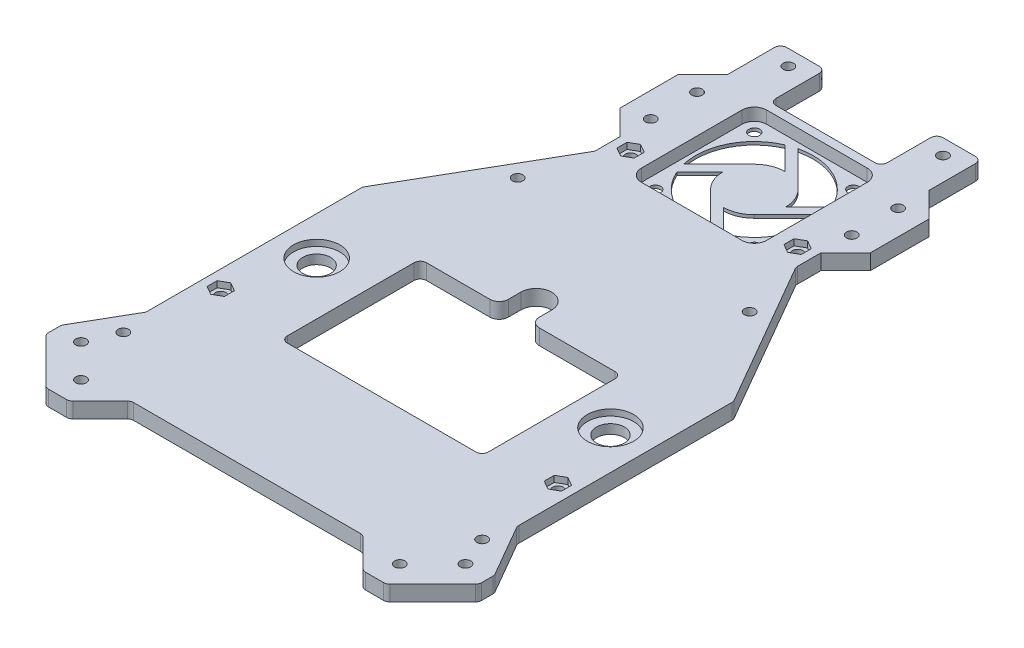
SolidWorks part; units mm, degrees
material "ABS PC"
ref_plane "Front Plane" through (0, 0, 0) normal (0, 0, 1) x (1, 0, 0)
ref_plane "Top Plane" through (0, 0, 0) normal (0, 1, 0) x (1, 0, 0)
ref_plane "Right Plane" through (0, 0, 0) normal (1, 0, 0) x (0, 0, -1)
sketch "Sketch1" plane through (0, 0, 0) normal (0, 1, 0) x (1, 0, 0)
  line L1 (70, -110) -> (-70, -110)
  line L2 (70, -110) -> (70, 110)
  line L3 (70, 110) -> (-70, 110)
  line L4 (-70, -110) -> (-70, 110)
  line L5 (70, -110) -> (-70, 110) construction
  line L6 (70, 110) -> (-70, -110) construction
  point P0 (0, 0)
  dimension "D1" = 220
  dimension "D2" = 140
extrude "Boss-Extrude1" add sketch "Sketch1" along normal blind 5
sketch "Sketch8" plane through (0, 5, 0) normal (0, 1, 0) x (1, 0, 0)
  line L0 (-70, 110) -> (-32.5, 110)
  line L1 (70, 110) -> (-70, 110) construction
  line L2 (-32.5, 110) -> (-32.5, 44.9519)
  line L3 (-32.5, 44.9519) -> (-70, -20)
  line L4 (-70, 110) -> (-70, -110) construction
  line L5 (-70, 110) -> (-70, -20)
  line L6 (0, 110) -> (0, -110) construction
  line L7 (-70, -110) -> (70, -110) construction
  line L8 (70, 110) -> (70, -20)
  line L9 (32.5, 44.9519) -> (70, -20)
  line L10 (32.5, 110) -> (32.5, 44.9519)
  line L11 (70, 110) -> (32.5, 110)
  dimension "D1" = 130
  dimension "D2" = 30
  dimension "D3" = 65
extrude "Cut-Extrude1" cut sketch "Sketch8" against normal blind 5
chamfer "Chamfer3" distance 15 angle 45 2 edges at (70, 2.5, 110) (-70, 2.5, 110)
sketch "Sketch48" plane through (0, 5, 0) normal (0, 1, 0) x (1, 0, 0)
  line L0 (32.5, 110) -> (-32.5, 110) construction
  line L1 (34.2449, 70.5) -> (40.5, 70.5) construction
  line L2 (32.5, 53) -> (32.5, 88)
  line L4 (32.5, 88) -> (40.5, 80)
  line L5 (40.5, 80) -> (40.5, 61)
  line L6 (32.5, 53) -> (40.5, 61)
  line L7 (0, 71.0199) -> (0, 60.9015) construction
  line L8 (-32.5, 53) -> (-40.5, 61)
  line L9 (-40.5, 80) -> (-40.5, 61)
  line L10 (-32.5, 88) -> (-40.5, 80)
  line L11 (-32.5, 53) -> (-32.5, 88)
  line L13 (32.5, 110) -> (32.5, 44.9519) construction
  point P0 (32.5, 83)
  point P16 (-32.5, 70.5)
  point P21 (0, 0)
  point P22 (36.7334, 83)
  dimension "D1" = 45
  dimension "D2" = 8
  dimension "D3" = 35
  dimension "D4" = 39.5
extrude "Boss-Extrude4" add sketch "Sketch48" against normal up to surface (5 mm away) up to face at (0, 0, 14.0096)
sketch "Sketch10" plane through (0, 0, 0) normal (0, 1, 0) x (1, 0, 0)
  line L0 (0, 110) -> (0, -110) construction
  line L1 (32.5, 110) -> (-32.5, 110) construction
  line L2 (-55, -110) -> (55, -110) construction
  line L3 (-32.5, 78) -> (-32.5, 63) construction
  line L4 (-62.5, -102.5) -> (-56.8431, -96.8431) construction
  line L5 (-62.1464, -91.5398) -> (-51.5398, -102.1464) construction
  line L6 (-70, -95) -> (-55, -110) construction
  point P9 (32.5, 63)
  point P10 (32.5, 78)
  point P17 (51.5398, -102.1464)
  point P18 (62.1464, -91.5398)
  dimension "D1" = 15
  dimension "D2" = 65
  dimension "D3" = 32
  dimension "D4" = 15
  dimension "D5" = 8
sketch "Sketch15" plane through (0, 5, 0) normal (0, 1, 0) x (1, 0, 0)
  line L0 (0, 110) -> (0, -110) construction
  line L1 (32.5, 110) -> (-32.5, 110) construction
  line L2 (-55, -110) -> (55, -110) construction
  line L3 (25, 100) -> (-25, 100) construction
  line L4 (37.5, 25) -> (-37.5, 25) construction
  line L5 (58, -57) -> (-58, -57) construction
  point P9 (0, 100)
  point P13 (0, 25)
  point P15 (0, -57)
  dimension "D1" = 50
  dimension "D2" = 10
  dimension "D3" = 75
  dimension "D4" = 85
  dimension "D5" = 116
  dimension "D6" = 167
hole_wizard "CSK for M3 Flat Head Machine Screw3" positions "Sketch16" profile "Sketch17" countersink size "M3" standard "ANSI Metric"
sketch "Sketch16" plane through (0, 0, 0) normal (0, 1, 0) x (1, 0, 0)
  point P6 (37.5, 25)
  point P9 (-37.5, 25)
  point P12 (-25, 100)
  point P15 (25, 100)
sketch "Sketch17" plane through (37.5, 0, -25) normal (1, 0, 0) x (0, 0, -1)
  line L0 (0, 0) -> (0, 6.0215)
  line L1 (0, 6.0215) -> (1.7, 5)
  line L2 (1.7, 5) -> (1.7, 1.45)
  line L3 (1.7, 1.45) -> (3.15, 0)
  line L5 (3.15, 0) -> (0, 0)
  line L6 (-1.7, 1.45) -> (-3.15, 0) construction
  line L10 (0, 6.0215) -> (-1.7, 5) construction
  line L11 (0, -6.35) -> (0, 107.95) construction
  dimension "Hole Dia." = 3.4
  dimension "Hole Depth" = 5
  dimension "Near C'Sink Dia." = 6.3
  dimension "Near C'Sink Angle" = 90
  dimension "Drill Angle" = 118
sketch "Sketch18" plane through (0, 5, 0) normal (0, 1, 0) x (1, 0, 0)
  line L0 (32.5, 110) -> (-32.5, 110) construction
  line L1 (-46.4338, 114.6286) -> (34.8035, 114.6286)
  line L2 (-46.4338, 114.6286) -> (-46.4338, 105)
  line L3 (-46.4338, 105) -> (34.8035, 105)
  line L4 (34.8035, 114.6286) -> (34.8035, 105)
  dimension "D1" = 5
extrude "Cut-Extrude2" cut sketch "Sketch18" against normal blind 5
sketch "Sketch34" plane through (0, 5, 0) normal (0, 1, 0) x (1, 0, 0)
  line L0 (-70, -20) -> (-60, -2.6795)
  line L1 (-70, -20) -> (-32.5, 44.9519) construction
  line L2 (-60, -2.6795) -> (-60, -72.6795)
  line L3 (-60, -72.6795) -> (-70, -90)
  line L4 (-70, -20) -> (-70, -95) construction
  line L5 (-70, -90) -> (-70, -20)
  line L6 (0, -90.4055) -> (0, -61.6307) construction
  line L7 (70, -90) -> (70, -20)
  line L8 (60, -72.6795) -> (70, -90)
  line L9 (60, -2.6795) -> (60, -72.6795)
  line L10 (70, -20) -> (60, -2.6795)
  line L11 (-55, -110) -> (55, -110) construction
  dimension "D1" = 120
  dimension "D2" = 20
extrude "Cut-Extrude8" cut sketch "Sketch34" against normal blind 10
chamfer "Chamfer4" [suppressed] distance 20 angle 30
sketch "Sketch35" plane through (0, 5, 0) normal (0, 1, 0) x (1, 0, 0)
  line L1 (-30.5, -58.5) -> (34.5, -58.5)
  line L2 (-30.5, -58.5) -> (-30.5, -13.5)
  line L3 (-30.5, -13.5) -> (34.5, -13.5)
  line L4 (34.5, -58.5) -> (34.5, -13.5)
  line L5 (-30.5, -58.5) -> (34.5, -13.5) construction
  line L6 (-30.5, -13.5) -> (34.5, -58.5) construction
  point P0 (2, -36)
  dimension "D1" = 2
  dimension "D2" = 65
  dimension "D3" = 45
  dimension "D4" = 36
extrude "Cut-Extrude9" cut sketch "Sketch35" against normal through all
fillet "Fillet1" radius 2 4 edges at (-30.5, 2.5, 58.5) (-30.5, 2.5, 13.5) (34.5, 2.5, 13.5) (34.5, 2.5, 58.5)
sketch "Sketch36" plane through (0, 5, 0) normal (0, 1, 0) x (1, 0, 0)
  line L0 (0, -110) -> (0, -100) construction
  line L1 (-55, -110) -> (55, -110) construction
  line L2 (-47.5, -110) -> (-37.5, -100)
  line L3 (-37.5, -100) -> (37.5, -100)
  line L4 (-47.5, -110) -> (47.5, -110)
  line L6 (-70, -95) -> (-55, -110) construction
  line L7 (47.5, -110) -> (37.5, -100)
  dimension "D1" = 10
  dimension "D2" = 95
extrude "Cut-Extrude10" cut sketch "Sketch36" against normal through all
sketch "Sketch38" plane through (0, 0, 0) normal (0, -1, 0) x (1, 0, 0)
  line L0 (0, -105) -> (0, -90) construction
  line L1 (-32.5, -105) -> (32.5, -105) construction
  line L2 (18, -87) -> (-18, -87)
  line L3 (-18, -87) -> (-18, -105)
  line L4 (-18, -105) -> (18, -105)
  line L5 (18, -87) -> (18, -105)
  dimension "D1" = 90
  dimension "D2" = 18
  dimension "D3" = 36
extrude "Cut-Extrude14" cut sketch "Sketch38" against normal through all
sketch "Sketch39" plane through (0, 0, 0) normal (0, -1, 0) x (1, 0, 0)
  line L0 (0, 37.973) -> (0, 15.9654) construction
  circle A0 centre (-47.5, 30) radius 4.5
  circle A1 centre (47.5, 30) radius 4.5
  dimension "D1" = 95
  dimension "D2" = 9
  dimension "D3" = 30
extrude "Cut-Extrude15" cut sketch "Sketch39" against normal through all
hole_wizard "CSK for M3 Flat Head Machine Screw2" positions "Sketch40" profile "Sketch41" countersink size "M3" standard "ANSI Metric"
sketch "Sketch40" plane through (0, 0, 0) normal (0, -1, 0) x (-1, 0, 0)
  point P0 (-58, -82)
  point P3 (58, -82)
sketch "Sketch41" plane through (58, 0, 82) normal (1, 0, 0) x (0, 0, -1)
  line L0 (0, 0) -> (0, 11.0215)
  line L1 (0, 11.0215) -> (1.7, 10)
  line L2 (1.7, 10) -> (1.7, 1.45)
  line L3 (1.7, 1.45) -> (3.15, 0)
  line L5 (3.15, 0) -> (0, 0)
  line L6 (-1.7, 1.45) -> (-3.15, 0) construction
  line L10 (0, 11.0215) -> (-1.7, 10) construction
  line L11 (0, -6.35) -> (0, 107.95) construction
  dimension "Hole Dia." = 3.4
  dimension "Hole Depth" = 10
  dimension "Near C'Sink Dia." = 6.3
  dimension "Near C'Sink Angle" = 90
  dimension "Drill Angle" = 118
hole_wizard "Ø3.5 (3.5) Diameter Hole1" positions "Sketch45" profile "Sketch46" hole size "Ø3.5" standard "ANSI Metric"
sketch "Sketch45" plane through (0, 5, 0) normal (0, 1, 0) x (1, 0, 0)
  line L0 (-32.5, 44.9519) -> (-32.5, 53) construction
  line L1 (-60, -72.6795) -> (-60, -2.6795) construction
  line L2 (-32.5, 105) -> (-18, 105) construction
  point P0 (-54.5, -54)
  point P2 (-27, 51)
  dimension "D1" = 5.5
  dimension "D2" = 5.5
  dimension "D3" = 54
  dimension "D4" = 105
sketch "Sketch46" plane through (-54.5, 5, 54) normal (1, 0, 0) x (0, 0, 1)
  line L0 (0, 0) -> (0, 6.0515)
  line L1 (0, 6.0515) -> (1.75, 5)
  line L2 (1.75, 5) -> (1.75, 0)
  line L5 (1.75, 0) -> (0, 0)
  line L10 (0, 6.0515) -> (-1.75, 5) construction
  line L11 (0, -6.35) -> (0, 107.95) construction
  dimension "Hole Dia." = 3.5
  dimension "Hole Depth" = 5
  dimension "Drill Angle" = 118
mirror "Mirror1" about plane through (0, 0, 0) normal (1, 0, 0) of "Ø3.5 (3.5) Diameter Hole1"
sketch "Sketch47" plane through (0, 5, 0) normal (0, 1, 0) x (1, 0, 0)
  line L0 (0, 13.2168) -> (0, -3.9151) construction
  line L1 (29.8, 49.3834) -> (29.8, 52.6166)
  line L2 (29.8, 52.6166) -> (27, 54.2332)
  line L3 (27, 54.2332) -> (24.2, 52.6166)
  line L4 (24.2, 52.6166) -> (24.2, 49.3834)
  line L5 (24.2, 49.3834) -> (27, 47.7668)
  line L6 (27, 47.7668) -> (29.8, 49.3834)
  line L7 (57.3, -55.6166) -> (57.3, -52.3834)
  line L8 (57.3, -52.3834) -> (54.5, -50.7668)
  line L9 (54.5, -50.7668) -> (51.7, -52.3834)
  line L10 (51.7, -52.3834) -> (51.7, -55.6166)
  line L11 (51.7, -55.6166) -> (54.5, -57.2332)
  line L12 (54.5, -57.2332) -> (57.3, -55.6166)
  line L13 (-54.5, -57.2332) -> (-57.3, -55.6166)
  line L14 (-51.7, -55.6166) -> (-54.5, -57.2332)
  line L15 (-51.7, -52.3834) -> (-51.7, -55.6166)
  line L16 (-54.5, -50.7668) -> (-51.7, -52.3834)
  line L17 (-57.3, -52.3834) -> (-54.5, -50.7668)
  line L18 (-57.3, -55.6166) -> (-57.3, -52.3834)
  line L19 (-27, 47.7668) -> (-29.8, 49.3834)
  line L20 (-24.2, 49.3834) -> (-27, 47.7668)
  line L21 (-24.2, 52.6166) -> (-24.2, 49.3834)
  line L22 (-27, 54.2332) -> (-24.2, 52.6166)
  line L23 (-29.8, 52.6166) -> (-27, 54.2332)
  line L24 (-29.8, 49.3834) -> (-29.8, 52.6166)
  circle A0 centre (27, 51) radius 2.8 construction
  circle A1 centre (54.5, -54) radius 2.8 construction
  circle A2 centre (-54.5, -54) radius 2.8 construction
  circle A3 centre (-27, 51) radius 2.8 construction
  dimension "D1" = 5.6
extrude "Cut-Extrude16" cut sketch "Sketch47" against normal blind 2
hole_wizard "CSK for M3 Flat Head Machine Screw1" positions "Sketch52" profile "Sketch53" countersink size "M3" standard "ANSI Metric"
sketch "Sketch52" plane through (0, 0, 0) normal (0, -1, 0) x (-1, 0, 0)
  point P0 (32.5, 63)
  point P3 (32.5, 78)
  point P6 (-32.5, 78)
  point P9 (-32.5, 63)
  point P12 (62.1464, -91.5398)
  point P15 (51.5398, -102.1464)
  point P18 (-51.5398, -102.1464)
  point P21 (-62.1464, -91.5398)
sketch "Sketch53" plane through (-32.5, 0, -63) normal (1, 0, 0) x (0, 0, -1)
  line L0 (0, 0) -> (0, 6.0215)
  line L1 (0, 6.0215) -> (1.7, 5)
  line L2 (1.7, 5) -> (1.7, 1.45)
  line L3 (1.7, 1.45) -> (3.15, 0)
  line L5 (3.15, 0) -> (0, 0)
  line L6 (-1.7, 1.45) -> (-3.15, 0) construction
  line L10 (0, 6.0215) -> (-1.7, 5) construction
  line L11 (0, -6.35) -> (0, 107.95) construction
  dimension "Hole Dia." = 3.4
  dimension "Hole Depth" = 5
  dimension "Near C'Sink Dia." = 6.3
  dimension "Near C'Sink Angle" = 90
  dimension "Drill Angle" = 118
fillet "Fillet3" radius 2 22 edges at (-32.5, 2.5, -105) (-32.5, 2.5, -44.9519) (-60, 2.5, 2.6795) (-60, 2.5, 72.6795) (-70, 2.5, 90) (-70, 2.5, 95) (-55, 2.5, 110) (-47.5, 2.5, 110) (-37.5, 2.5, 100) (37.5, 2.5, 100) (47.5, 2.5, 110) (55, 2.5, 110) (70, 2.5, 95) (70, 2.5, 90) (60, 2.5, 72.6795) (60, 2.5, 2.6795) (32.5, 2.5, -44.9519) (18, 2.5, -105) (18, 2.5, -87) (-18, 2.5, -87) (-18, 2.5, -105) (32.5, 2.5, -105)
sketch "Sketch54" plane through (0, 5, 0) normal (0, 1, 0) x (1, 0, 0)
  line L0 (0, -24.4413) -> (0, -37.1235) construction
  circle A0 centre (-47.5, -30) radius 7.5
  circle A1 centre (-47.5, -30) radius 4.5
  circle A2 centre (-47.5, -30) radius 4.5 construction
  circle A3 centre (47.5, -30) radius 4.5
  circle A4 centre (47.5, -30) radius 7.5
  dimension "D1" = 15
extrude "Cut-Extrude17" cut sketch "Sketch54" against normal blind 2
hole_wizard "Ø3.5 (3.5) Diameter Hole2" positions "Sketch55" profile "Sketch56" hole size "Ø3.5" standard "ANSI Metric" end condition through all
sketch "Sketch55" plane through (0, 5, 0) normal (0, 1, 0) x (1, 0, 0)
  line L1 (16, 80) -> (-16, 80) construction
  line L2 (16, 80) -> (16, 48) construction
  line L3 (16, 48) -> (-16, 48) construction
  line L4 (-16, 80) -> (-16, 48) construction
  line L5 (0, 48) -> (0, 0) construction
  point P1 (16, 80)
  point P2 (-16, 48)
  point P5 (16, 48)
  point P6 (-16, 80)
  dimension "D1" = 32
  dimension "D2" = 48
sketch "Sketch56" plane through (16, 5, -80) normal (1, 0, 0) x (0, 0, 1)
  line L0 (0, 0) -> (0, 5)
  line L1 (0, 5) -> (1.75, 5)
  line L2 (1.75, 5) -> (1.75, 0)
  line L5 (1.75, 0) -> (0, 0)
  line L11 (0, -6.35) -> (0, 107.95) construction
  dimension "Thru Hole Dia." = 3.5
  dimension "Thru Hole Depth" = 5
sketch "Sketch57" plane through (0, 5, 0) normal (0, 1, 0) x (1, 0, 0)
  line L0 (-16, 80) -> (16, 48) construction
  line L1 (9.9995, 64.1) -> (17.4397, 71.5402)
  line L2 (7.0711, 56.9289) -> (18.4947, 68.3526)
  line L3 (0.1, 54.0005) -> (7.5402, 46.5603)
  line L4 (-7.0711, 56.9289) -> (4.3526, 45.5053)
  line L5 (-9.9995, 63.9) -> (-17.4397, 56.4598)
  line L6 (-7.0711, 71.0711) -> (-18.4947, 59.6474)
  line L7 (-0.1, 73.9995) -> (-7.5402, 81.4397)
  line L8 (7.0711, 71.0711) -> (-4.3526, 82.4947)
  line L9 (0, 58.5149) -> (0, 69.4851) construction
  circle A0 centre (0, 64) radius 19
  circle A1 centre (0, 64) radius 10
  point P31 (0, 64)
  dimension "D1" = 38
  dimension "D2" = 20
  dimension "D3" = 3
  dimension "D5" = 135
  dimension "D4" = 4
extrude "Cut-Extrude18" cut sketch "Sketch57" against normal blind 10 contours A1 L7 A0 L6 | A1 L1 A0 L8 | A1 L3 A0 L2 | A1 L5 A0 L4 region at (7.9912, 5, -75.4298) region at (11.4298, 5, -56.0088) region at (-11.4298, 5, -71.9912) region at (-7.9912, 5, -52.5702)
sketch "Sketch58" plane through (0, 5, 0) normal (0, 1, 0) x (1, 0, 0)
  line L1 (-16.25, 43.75) -> (16.25, 43.75)
  line L2 (-20.25, 47.75) -> (-20.25, 80.25)
  line L3 (-16.25, 84.25) -> (16.25, 84.25)
  line L4 (20.25, 47.75) -> (20.25, 80.25)
  line L5 (-20.25, 43.75) -> (20.25, 84.25) construction
  line L6 (-20.25, 84.25) -> (20.25, 43.75) construction
  arc A0 (-20.25, 47.75) -> (-16.25, 43.75) centre (-16.25, 47.75) ccw
  arc A1 (16.25, 43.75) -> (20.25, 47.75) centre (16.25, 47.75) ccw
  arc A2 (20.25, 80.25) -> (16.25, 84.25) centre (16.25, 80.25) ccw
  arc A3 (-16.25, 84.25) -> (-20.25, 80.25) centre (-16.25, 80.25) ccw
  point P0 (0, 64)
  dimension "D2" = 4
  dimension "D1" = 40.5
extrude "Cut-Extrude20" cut sketch "Sketch58" against normal blind 4
sketch "Sketch59" plane through (0, 0, 0) normal (0, -1, 0) x (1, 0, 0)
  line L0 (32.5, 13.5) -> (-28.5, 13.5) construction
  line L1 (5, 6.5) -> (-5, 6.5)
  line L2 (5, 6.5) -> (5, 13.5)
  line L3 (5, 13.5) -> (-5, 13.5)
  line L4 (-5, 6.5) -> (-5, 13.5)
  line L5 (5, 6.5) -> (-5, 13.5) construction
  line L6 (5, 13.5) -> (-5, 6.5) construction
  line L7 (0, 0) -> (0, 10) construction
  arc A0 (-5, 6.5) -> (5, 6.5) centre (0, 6.5) ccw
  point P0 (0, 10)
  dimension "D1" = 7
  dimension "D2" = 10
extrude "Cut-Extrude21" cut sketch "Sketch59" against normal blind 10 contours L4 L1 L2 L3 | L1 A0 region at (0, 0, 4.3779) region at (0, 0, 10)
fillet "Fillet5" radius 3 2 edges at (5, 2.5, 13.5) (-5, 2.5, 13.5)
